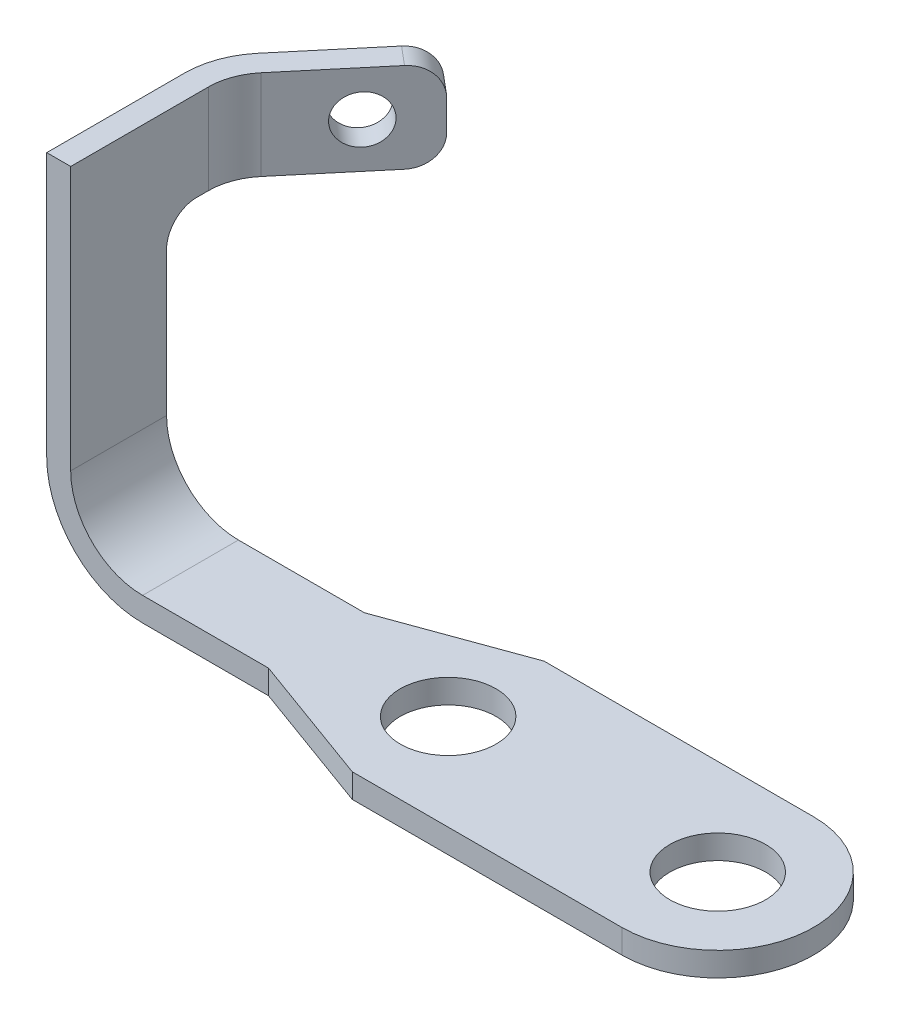
SolidWorks part; units mm, degrees
ref_plane "Front Plane" through (0, 0, 0) normal (0, 0, 1) x (1, 0, 0)
ref_plane "Top Plane" through (0, 0, 0) normal (0, 1, 0) x (1, 0, 0)
ref_plane "Right Plane" through (0, 0, 0) normal (1, 0, 0) x (0, 0, -1)
sketch "Sketch1" plane through (0, 0, 0) normal (0, 0, 1) x (1, 0, 0)
  line L0 (0, 0) -> (-104, 0)
  line L1 (-120, 16) -> (-120, 60)
  arc A0 (-104, 0) -> (-120, 16) centre (-104, 16) cw
  dimension "D1" = 16
  dimension "D2" = 120
  dimension "D3" = 60
extrude "Extrude-Thin1" add sketch "Sketch1" along normal blind 16 thin thin type one direction wall 4
sketch "Sketch2" plane through (0, 4, 0) normal (0, 1, 0) x (1, 0, 0)
  line L0 (0, -16) -> (0, 0) construction
  line L1 (-16, 8) -> (-61, 8)
  line L2 (-16, -24) -> (-61, -24)
  line L3 (-61, 8) -> (-82.9798, 0)
  line L4 (0, 0) -> (-104, 0) construction
  line L5 (-61, -24) -> (-82.9798, -16)
  line L6 (0, -16) -> (-104, -16) construction
  line L7 (-82.9798, 0) -> (-82.9798, -16)
  circle A0 centre (-16, -8) radius 16
  circle A2 centre (-61, -8) radius 8
  circle A3 centre (-16, -8) radius 8
  point P5 (0, -8)
  line M3 (0, 0) -> (-104, 0)
  line M5 (-104, -16) -> (0, -16)
  dimension "D1" = 32
  dimension "D2" = 16
  dimension "D4" = 40
  dimension "D3" = 45
extrude "Cut-Extrude-Thin1" cut sketch "Sketch2" against normal blind 10 thin contours A0 thin type one direction wall 4
extrude "Boss-Extrude1" add sketch "Sketch2<5>" against normal blind 4 contours A0 L1 L3 M3 | A0 L5 L2 M5 | A2 A0 M5 M3 | A0 M5 | A0 M3 | A3 A0 M3 M5 region at (-49.2351, 4, -3.8358) region at (-16, 4, -3.2803) region at (-26.64, 4, 8) region at (-43.0709, 4, 8) region at (-16, 4, 19.2803) region at (-49.2351, 4, 19.8358)
sketch "Sketch2<5>" plane through (0, 4, 0) normal (0, 1, 0) x (1, 0, 0) same geometry as "Sketch2"
extrude "Cut-Extrude1" cut sketch "Sketch2<6>" against normal blind 4 contours A2 | A3 region at (-61, 4, 8) region at (-16, 4, 8)
sketch "Sketch2<6>" plane through (0, 4, 0) normal (0, 1, 0) x (1, 0, 0) same geometry as "Sketch2"
sketch "Sketch3" plane through (0, 60, 0) normal (0, 1, 0) x (1, 0, 0)
  line L0 (-116, 0) -> (-116, 7)
  line L1 (-113.6604, 13.4279) -> (-99.5191, 30.2809)
  line L2 (-82.9798, 0) -> (-104, 0) construction
  arc A0 (-116, 7) -> (-113.6604, 13.4279) centre (-106, 7) cw
  point P6 (-116, 3.5)
  dimension "D1" = 10
  dimension "D2" = 22
  dimension "D3" = 7
  dimension "D4" = 50
extrude "Extrude-Thin2" add sketch "Sketch3" against normal blind 15 thin thin type one direction reverse wall 4
fillet "Fillet1" radius 5 1 edges at (-118, 45, 0)
fillet "Fillet2" radius 5 2 edges at (-101.0512, 45, -31.5664) (-101.0512, 60, -31.5664)
sketch "Sketch5" plane through (-73.3106, 0, -61.5149) normal (0.766, 0, 0.6428) x (0.6428, 0, -0.766)
  line L0 (-40.7732, 50) -> (-40.7732, 55) construction
  circle A0 centre (-50.7732, 52.5) radius 4
  point P4 (-40.7732, 52.5)
  dimension "D1" = 8
  dimension "D2" = 10
extrude "Cut-Extrude2" cut sketch "Sketch5" against normal blind 15
